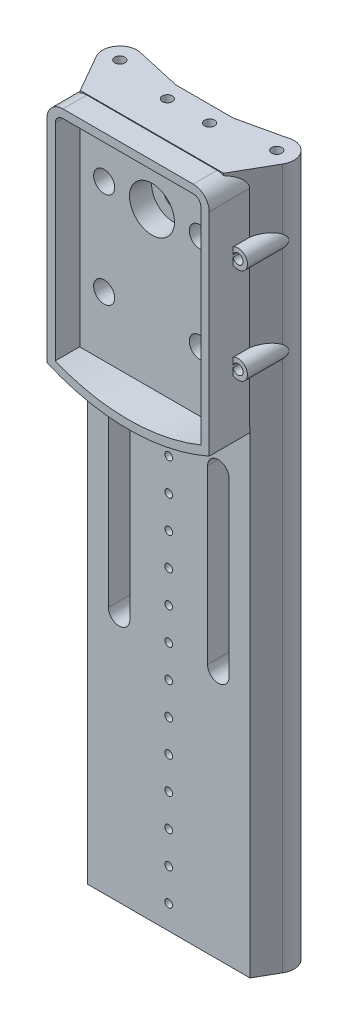
SolidWorks part; units mm, degrees
material "ABS"
ref_plane "前视基准面" through (0, 0, 0) normal (0, 0, 1) x (1, 0, 0)
ref_plane "上视基准面" through (0, 0, 0) normal (0, 1, 0) x (1, 0, 0)
ref_plane "右视基准面" through (0, 0, 0) normal (1, 0, 0) x (0, 0, -1)
sketch "草图2" plane through (0, 0, 0) normal (0, 0, 1) x (1, 0, 0)
  line L1 (-20, 20) -> (20, 20) construction
  line L2 (-20, 20) -> (-20, -20) construction
  line L3 (-20, -20) -> (20, -20) construction
  line L4 (20, 20) -> (20, -20) construction
  line L5 (-20, 20) -> (20, -20) construction
  line L6 (-20, -20) -> (20, 20) construction
  line L7 (-30, 45) -> (30, 45)
  line L8 (-30, 45) -> (-30, -45)
  line L9 (-30, -45) -> (30, -45)
  line L10 (30, 45) -> (30, -45)
  line L11 (-30, 45) -> (30, -45) construction
  line L12 (-30, -45) -> (30, 45) construction
  circle A0 centre (20, 20) radius 4.4
  circle A1 centre (-20, 20) radius 4.4
  circle A2 centre (-20, -20) radius 4.4
  circle A3 centre (20, -20) radius 4.4
  point P0 (0, 0)
  point P10 (0, 0)
extrude "凸台-拉伸1" add sketch "草图2" along normal blind 7
sketch "草图3" plane through (0, 0, 0) normal (0, 0, -1) x (-1, 0, 0)
  circle A0 centre (0, 20) radius 9.4
extrude "切除-拉伸1" cut sketch "草图3" against normal blind 29 contours A0
sketch "草图5" plane through (0, 0, 0) normal (0, 0, -1) x (-1, 0, 0)
  line L14 (30, -45) -> (30, 45)
  line L15 (-30, -45) -> (30, -45)
  line L16 (-30, 45) -> (-30, -45)
  line L17 (30, 45) -> (-30, 45)
  line L18 (30, -45) -> (30, 45)
  line L19 (-30, -45) -> (30, -45)
  line L20 (-30, 45) -> (-30, -45)
  line L21 (30, 45) -> (-30, 45)
  circle A2 centre (0, 20) radius 9.4
  circle A3 centre (0, 20) radius 9.4
  circle A5 centre (-20, 20) radius 4.4
  circle A6 centre (-20, 20) radius 4.4
  circle A8 centre (20, 20) radius 4.4
  circle A9 centre (20, 20) radius 4.4
  circle A11 centre (-20, -20) radius 4.4
  circle A12 centre (-20, -20) radius 4.4
  circle A14 centre (20, -20) radius 4.4
  circle A15 centre (20, -20) radius 4.4
  dimension "D1" = 0
  dimension "D2" = 0
  dimension "D3" = 0
  dimension "D4" = 0
  dimension "D5" = 0
  dimension "D6" = 0
extrude "凸台-拉伸2" add sketch "草图5" along normal blind 0.2
sketch "草图6" plane through (0, 0, -0.2) normal (0, 0, -1) x (-1, 0, 0)
  circle A0 centre (-20, 20) radius 2.2
  circle A1 centre (20, 20) radius 2.2
  circle A2 centre (-20, -20) radius 2.2
  circle A3 centre (20, -20) radius 2.2
  circle A4 centre (-20, 20) radius 6.4
  circle A5 centre (20, 20) radius 6.4
  circle A6 centre (-20, -20) radius 6.4
  circle A7 centre (20, -20) radius 6.4
extrude "凸台-拉伸3" add sketch "草图6" along normal blind 5
sketch "草图8" plane through (0, 0, -0.2) normal (0, 0, -1) x (-1, 0, 0)
  line L0 (-1.1773, 20.238) -> (1.0682, 20.238) construction
  circle A0 centre (-0.0546, 20.238) radius 9.4
  circle A1 centre (-0.0546, 20.238) radius 10.4
extrude "凸台-拉伸4" add sketch "草图8" along normal blind 2
sketch "草图9" plane through (0, -45, 0) normal (0, -1, 0) x (1, 0, 0)
  line L0 (23.8, -5.2) -> (23.8, -19.2) construction
  line L1 (8.867, -4.0323) -> (10.6463, -3.4441)
  line L2 (10.6463, -3.4441) -> (12.4128, -4.7101)
  line L6 (12.4128, -4.7101) -> (13.9144, -7.9192)
  line L10 (13.6, -5.2) -> (26.4, -5.2) construction
  line L11 (23.8, -7.4) -> (23.8, -5.2) construction
  line L12 (23.8, -12.4) -> (32.8, -12.4) construction
  line L13 (0.0546, -2.2) -> (0, -32) construction
  line L14 (-10.3454, -2.2) -> (10.4546, -2.2) construction
  line L15 (-4, -32) -> (4, -32) construction
  line L17 (8.8362, -12.4322) -> (8.8296, -14.2322)
  line L18 (8.8296, -14.2322) -> (12.7368, -14.2465)
  line L19 (13.9144, -7.9192) -> (13.355, -12.4323)
  line L20 (13.355, -12.4323) -> (12.7368, -14.2465)
  line L21 (-8.7645, -4) -> (-10.5417, -3.4053)
  line L22 (-10.5417, -3.4053) -> (-12.3128, -4.6648)
  line L23 (-12.3128, -4.6648) -> (-13.8261, -7.8684)
  line L24 (-13.8261, -7.8684) -> (-13.2832, -12.3835)
  line L25 (-13.2832, -12.3835) -> (-12.6717, -14.2)
  line L26 (-8.7645, -14.2) -> (-12.6717, -14.2)
  line L27 (-8.7645, -12.4) -> (-8.7645, -14.2)
  circle A1 centre (32.8, -12.4) radius 4.2
  circle A2 centre (32.8, -12.4) radius 6.2
  circle A3 centre (-32.728, -12.28) radius 4.2
  circle A4 centre (-32.728, -12.28) radius 6.2
  arc A5 (8.867, -4.0323) -> (8.8362, -12.4322) centre (8.8516, -8.2323) cw
  arc A6 (-8.7645, -4) -> (-8.7645, -12.4) centre (-8.7645, -8.2) ccw
extrude "凸台-拉伸6" add sketch "草图9" against normal blind 87 separate body
sketch "草图10" plane through (0, 0, -0.2) normal (0, 0, -1) x (-1, 0, 0)
  line L1 (20, -22) -> (20, -18) construction
  line L2 (0, 0) -> (0, -25.3032) construction
  circle A0 centre (-20, 20) radius 4.2
  circle A1 centre (20, 20) radius 4.2
  circle A3 centre (20, -20) radius 4.2
  circle A4 centre (-20, -20) radius 4.2
sketch "草图11" plane through (0, 45, 0) normal (0, 1, 0) x (1, 0, 0)
  line L1 (-30, -7) -> (-38.9787, 8.7067)
  line L2 (-12, 15) -> (12, 15)
  line L3 (-12, 15) -> (12, 15)
  line L4 (0, 41.8508) -> (0, 28.715) construction
  line L5 (30, -7) -> (38.9787, 8.7067)
  line L6 (-12, 15) -> (-31.1488, 19.3047)
  line L7 (12, 15) -> (31.1488, 19.3047)
  line L8 (-29.7984, -3.9169) -> (-29.5029, -3.4)
  line L9 (29.8515, -3.9169) -> (29.8515, -5.0995)
  line L10 (29.8515, -5.0995) -> (30, -7)
  line L12 (-29.7984, -3.9169) -> (-29.7984, -6.6215)
  line L13 (-29.7984, -6.6215) -> (-30, -7)
  line L14 (29.8515, -3.9169) -> (29.5232, -3.4)
  line L27 (-29.5029, -3.4) -> (29.5232, -3.4)
  circle A0 centre (-8.7645, 8.2) radius 4.2
  circle A1 centre (8.8516, 8.2323) radius 4.2
  circle A2 centre (-32.728, 12.28) radius 4.2
  circle A3 centre (32.8, 12.4) radius 4.2
  circle A7 centre (32.8, 12.4) radius 7.2
  arc A8 (38.9458, 8.649) -> (30.0689, 19.0619) centre (32.8, 12.4) ccw
  circle A10 centre (-32.728, 12.28) radius 7.2
  arc A11 (-31.1488, 19.3047) -> (-38.9787, 8.7067) centre (-32.728, 12.28) ccw
  line M11 (30, -7) -> (30, 0.2)
  line M12 (30, 0.2) -> (-30, 0.2)
  line M13 (-30, 0.2) -> (-30, -7)
  dimension "D2" = 1
  dimension "D1" = 1
  dimension "D3" = 1
extrude "凸台-拉伸11" add sketch "草图11" against normal up to surface (90 mm away) contours L6 A11 L1 L5 A8 L7 L3 A0 A1 A2 A3 M13 M12 M11 region at (0.0567, 45, -7.1387) region at (-38.3551, 45, -16.4374) region at (27.4758, 45, -7.8611) up to face at (0, -45, 3.4)
extrude "切除-拉伸2" cut sketch "草图10" along normal blind 74
sketch "草图12" plane through (0, 0, 7) normal (0, 0, 1) x (1, 0, 0)
  circle A0 centre (0, 20) radius 9.4
extrude "切除-拉伸3" cut sketch "草图12" against normal blind 9.2
sketch "草图13" plane through (0, 0, -0.2) normal (0, 0, 1) x (1, 0, 0)
  line L0 (0, 0) -> (0, -22.6477) construction
  circle A4 centre (-20, 20) radius 5.3944
  circle A5 centre (-20, -20) radius 5.555
  circle A6 centre (20, -20) radius 5.555
  circle A7 centre (20, 20) radius 5.3944
extrude "凸台-拉伸13" add sketch "草图13" against normal blind 5
sketch "草图14" plane through (0, 0, 7) normal (0, 0, 1) x (1, 0, 0)
  circle A0 centre (-20, 20) radius 2.1
  circle A1 centre (20, 20) radius 2.1
  circle A2 centre (20, -20) radius 2.1
  circle A3 centre (-20, -20) radius 2.1
  circle A4 centre (0, 20) radius 4.2
extrude "切除-拉伸4" cut sketch "草图14" against normal blind 88
sketch "草图15" plane through (0, 45, 0) normal (0, 1, 0) x (1, 0, 0)
  line L37 (30.0689, 19.0619) -> (12, 15)
  line L38 (30, -7) -> (38.9458, 8.649)
  line L39 (-30, -7) -> (30, -7)
  line L40 (-38.9787, 8.7067) -> (-30, -7)
  line L41 (-12, 15) -> (-31.1488, 19.3047)
  line L42 (12, 15) -> (-12, 15)
  line L43 (30.0689, 19.0619) -> (12, 15)
  line L44 (30, -7) -> (38.9458, 8.649)
  line L45 (-30, -7) -> (30, -7)
  line L46 (-38.9787, 8.7067) -> (-30, -7)
  line L47 (-12, 15) -> (-31.1488, 19.3047)
  line L48 (12, 15) -> (-12, 15)
  circle A0 centre (-32.728, 12.28) radius 2.1
  circle A1 centre (-8.7645, 8.2) radius 2.1
  circle A2 centre (8.8516, 8.2323) radius 2.1
  circle A3 centre (32.8, 12.4) radius 2.1
  arc A16 (38.9458, 8.649) -> (30.0689, 19.0619) centre (32.8, 12.4) ccw
  arc A17 (-31.1488, 19.3047) -> (-38.9787, 8.7067) centre (-32.728, 12.28) ccw
  arc A18 (38.9458, 8.649) -> (30.0689, 19.0619) centre (32.8, 12.4) ccw
  arc A19 (-31.1488, 19.3047) -> (-38.9787, 8.7067) centre (-32.728, 12.28) ccw
  dimension "D2" = 0
extrude "凸台-拉伸16" add sketch "草图15" along normal blind 3
sketch "草图16" plane through (0, -45, 0) normal (0, -1, 0) x (1, 0, 0)
  line L0 (-34.0015, 0) -> (34.0015, 0)
  line L1 (-38.9787, -8.7067) -> (-30, 7) construction
  line L2 (38.9458, -8.649) -> (30, 7) construction
  line L3 (34.0015, 0) -> (38.9458, -8.649)
  line L4 (-34.0015, 0) -> (-38.9787, -8.7067)
  line L5 (-31.1488, -19.3047) -> (-12, -15)
  line L6 (-12, -15) -> (12, -15)
  line L7 (12, -15) -> (30.0689, -19.0619)
  arc A0 (-38.9787, -8.7067) -> (-31.1488, -19.3047) centre (-32.728, -12.28) ccw
  arc A1 (38.9458, -8.649) -> (30.0689, -19.0619) centre (32.8, -12.4) cw
  circle A2 centre (-32.728, -12.28) radius 4.2
  circle A3 centre (-8.7645, -8.2) radius 4.2
  circle A4 centre (8.8516, -8.2323) radius 4.2
  circle A5 centre (32.8, -12.4) radius 4.2
extrude "凸台-拉伸17" add sketch "草图16" along normal blind 200
sketch "草图24" plane through (0, 0, 7) normal (0, 0, 1) x (1, 0, 0)
  line L0 (-27.25, 44) -> (27.25, 44) construction
  line L2 (-27.25, 47.7) -> (27.25, 47.7)
  line L3 (33.95, 41) -> (33.95, -47.5055)
  line L4 (30.25, 41) -> (30.25, -45.0604) construction
  line L5 (-30.25, 41) -> (-30.25, -45.0604) construction
  line L6 (-27.25, 44.2) -> (27.25, 44.2)
  line L7 (30.45, 41) -> (30.45, -45.1946)
  line L8 (-30.45, 41) -> (-30.45, -45.1946)
  line L9 (-33.95, 41) -> (-33.95, -47.5055)
  line L10 (-27.25, 47.5) -> (27.25, 47.5) construction
  line L11 (33.75, 41) -> (33.75, -47.3753) construction
  line L12 (-33.75, 41) -> (-33.75, -47.3753) construction
  arc A0 (-27.25, 44) -> (-30.25, 41) centre (-27.25, 41) ccw construction
  arc A1 (27.25, 44) -> (30.25, 41) centre (27.25, 41) cw construction
  arc A4 (-30.25, -45.0604) -> (30.25, -45.0604) centre (0, 29) ccw construction
  arc A5 (27.25, 44.2) -> (30.45, 41) centre (27.25, 41) cw
  arc A6 (-30.45, -45.1946) -> (30.45, -45.1946) centre (0, 29) ccw
  arc A7 (-27.25, 44.2) -> (-30.45, 41) centre (-27.25, 41) ccw
  arc A8 (27.25, 47.7) -> (33.95, 41) centre (27.25, 41) cw
  arc A9 (-33.95, -47.5055) -> (33.95, -47.5055) centre (0, 29) ccw
  arc A10 (-27.25, 47.7) -> (-33.95, 41) centre (-27.25, 41) ccw
  arc A11 (27.25, 47.5) -> (33.75, 41) centre (27.25, 41) cw construction
  arc A12 (-33.75, -47.3753) -> (33.75, -47.3753) centre (0, 29) ccw construction
  arc A13 (-27.25, 47.5) -> (-33.75, 41) centre (-27.25, 41) ccw construction
  dimension "D1" = 0.2
  dimension "D2" = 3.5
extrude "凸台-拉伸19" add sketch "草图24" along normal mid plane 20
sketch "草图26" plane through (0, 0, 0) normal (0, 0, 1) x (1, 0, 0)
  circle A0 centre (0, -208) radius 1.6
  circle A1 centre (0, -235) radius 1.6
extrude "切除-拉伸5" cut sketch "草图26" against normal blind 30
sketch "草图28" plane through (0, 0, 0) normal (0, 0, 1) x (1, 0, 0)
  line L0 (0, -206.4) -> (0, -194.5) construction
  line L1 (0, -178.4321) -> (0, -191.5679) construction
  circle A0 centre (0, -208) radius 1.6 construction
  circle A1 centre (0, -194.5) radius 1.6
extrude "切除-拉伸6" cut sketch "草图28" against normal through all
pattern_linear "阵列(线性)1" count 10 spacing 13.5 along (0, 1, 0) of "切除-拉伸6"
sketch "草图30" plane through (0, 0, 0) normal (0, 0, 1) x (1, 0, 0)
  line L6 (-20.7462, -68.3605) -> (-20.7462, -140.3605) construction
  line L7 (-16.2462, -68.3605) -> (-16.2462, -140.3605)
  line L8 (-25.2462, -68.3605) -> (-25.2462, -140.3605)
  line L9 (20.7462, -68.3605) -> (20.7462, -140.3605) construction
  line L10 (16.2462, -68.3605) -> (16.2462, -140.3605)
  line L11 (25.2462, -68.3605) -> (25.2462, -140.3605)
  arc A1 (-16.2462, -68.3605) -> (-25.2462, -68.3605) centre (-20.7462, -68.3605) ccw
  arc A2 (-25.2462, -140.3605) -> (-16.2462, -140.3605) centre (-20.7462, -140.3605) ccw
  arc A3 (16.2462, -68.3605) -> (25.2462, -68.3605) centre (20.7462, -68.3605) cw
  arc A4 (25.2462, -140.3605) -> (16.2462, -140.3605) centre (20.7462, -140.3605) cw
  point P6 (20.7462, -104.3605)
  point P17 (-20.7462, -104.3605)
extrude "切除-拉伸7" cut sketch "草图30" against normal through all
sketch "草图33" plane through (0, 0, 0) normal (0, 0, 1) x (1, 0, 0)
  line L0 (0, -208) -> (0, -235) construction
  circle A0 centre (0, -221.5) radius 1.6
extrude "切除-拉伸8" cut sketch "草图33" against normal through all
sketch "草图34" plane through (0, 0, 7) normal (0, 0, 1) x (1, 0, 0)
  line L0 (-20, 20) -> (-36, 20) construction
  line L4 (0, -20) -> (0, 20) construction
  line L5 (0, 0) -> (-20, 0) construction
  circle A0 centre (-36, 20) radius 2.1
  circle A3 centre (-36, 20) radius 3.928
  circle A8 centre (-36, -20) radius 2.1
  circle A9 centre (-36, -20) radius 3.928
extrude "凸台-拉伸20" add sketch "草图34" against normal up to surface (6.8224 mm away) up to face at (-34.3453, -49.4134, -0.6013)
ref_axis "基准轴1" through (0, 20, -15) along (0, 0, 1)
ref_plane "基准面1" through (0, 0, 0) normal (1, 0, 0) x (0, 0, -1)
sketch "草图36" plane through (0, 0, 7) normal (0, 0, 1) x (1, 0, 0)
  line L0 (0, -17.6) -> (0, 17.6) construction
  circle A1 centre (-36, -20) radius 3.928 construction
  circle A3 centre (-36, 20) radius 3.928 construction
  circle A8 centre (36, -20) radius 2.1
  circle A9 centre (36, -20) radius 3.928
  circle A10 centre (36, 20) radius 2.1
  circle A11 centre (36, 20) radius 3.928
extrude "凸台-拉伸21" add sketch "草图36" against normal up to surface (6.8224 mm away) up to face at (34.337, -49.4134, -0.5868)
